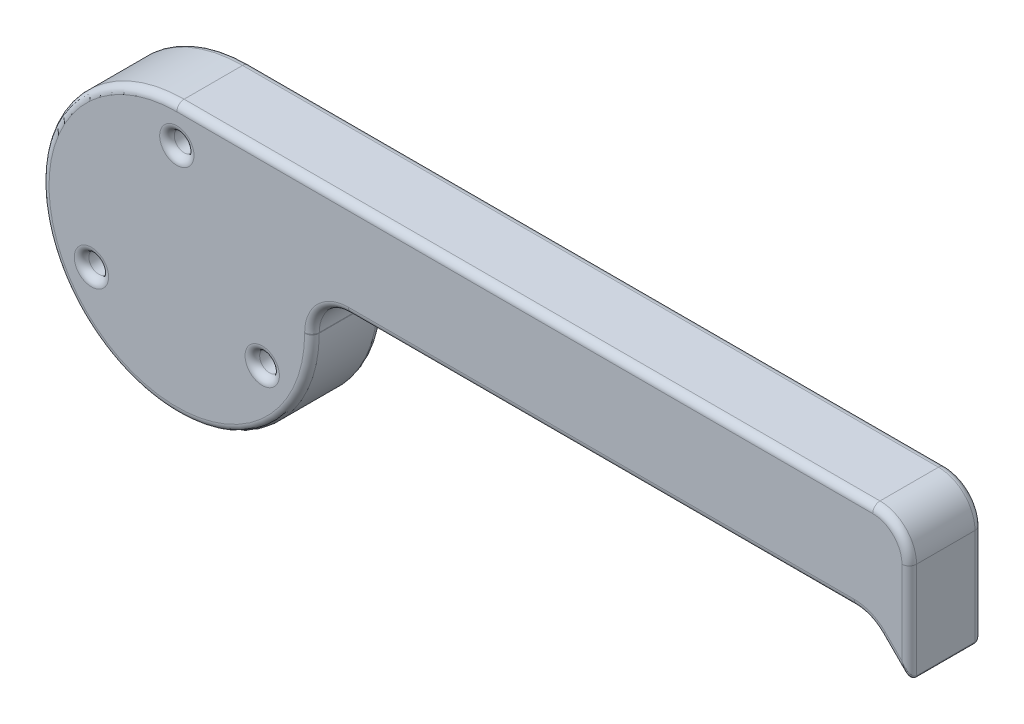
SolidWorks part; units mm, degrees
ref_plane "Front Plane" through (0, 0, 0) normal (0, 0, 1) x (1, 0, 0)
ref_plane "Top Plane" through (0, 0, 0) normal (0, 1, 0) x (1, 0, 0)
ref_plane "Right Plane" through (0, 0, 0) normal (1, 0, 0) x (0, 0, -1)
sketch "Sketch1" plane through (0, 0, 0) normal (0, 0, 1) x (1, 0, 0)
  line L0 (0, 18.5) -> (95.2706, 18.5)
  line L1 (100.2706, 13.5) -> (100.2706, 0.2706)
  line L2 (99.8087, 0.0793) -> (96.2731, 3.6148)
  line L4 (18.5, 0.0793) -> (18.5, 0)
  line L5 (92.7376, 5.0793) -> (23.5, 5.0793)
  line L6 (0, 0) -> (106.6522, 0) construction
  circle A0 centre (0, 0) radius 13.5 construction
  circle A1 centre (0, 13.5) radius 1.35
  circle A2 centre (11.6913, -6.75) radius 1.35
  circle A3 centre (-11.6913, -6.75) radius 1.35
  arc A4 (0, 18.5) -> (18.5, 0) centre (0, 0) ccw
  arc A5 (99.8087, 0.0793) -> (100.2706, 0.2706) centre (100, 0.2706) ccw
  arc A6 (95.2706, 18.5) -> (100.2706, 13.5) centre (95.2706, 13.5) cw
  arc A7 (96.2731, 3.6148) -> (92.7376, 5.0793) centre (92.7376, 0.0793) ccw
  arc A8 (23.5, 5.0793) -> (18.5, 0.0793) centre (23.5, 0.0793) ccw
  point P6 (0, 0)
  point P11 (0, 0)
  point P15 (68.5417, 3.468)
  point P16 (106.6522, 0.0493)
  point P20 (99.8016, 0.0879)
  point P21 (18.499, 5.0793)
  point P22 (19.2235, 5.0793)
  point P29 (94.8087, 5.0793)
  dimension "D1" = 2.7
  dimension "D3" = 27
  dimension "D4" = 0.5
  dimension "D5" = 5
  dimension "D9" = 45
  dimension "D8" = 5
  dimension "D6" = 5
  dimension "D7" = 100
  dimension "D2" = 3
extrude "Boss-Extrude1" add sketch "Sketch1" along normal blind 10
fillet "Fillet1" radius 1 26 edges at (-10.3413, -6.75, 0) (13.0413, -6.75, 0) (1.35, 13.5, 0) (18.5, 0.0396, 0) (19.9645, 3.6148, 0) (58.1188, 5.0793, 0) (94.651, 4.6987, 0) (98.0409, 1.847, 0) (100.1036, 0.0206, 0) (100.2706, 6.8853, 0) (98.8061, 17.0355, 0) (47.6353, 18.5, 0) (-13.0815, -13.0815, 0) (-10.3413, -6.75, 10) (1.35, 13.5, 10) (47.6353, 18.5, 10) (98.8061, 17.0355, 10) (100.2706, 6.8853, 10) (100.1036, 0.0206, 10) (98.0409, 1.847, 10) (94.651, 4.6987, 10) (58.1188, 5.0793, 10) (19.9645, 3.6148, 10) (18.5, 0.0396, 10) (-13.0815, -13.0815, 10) (13.0413, -6.75, 10)
